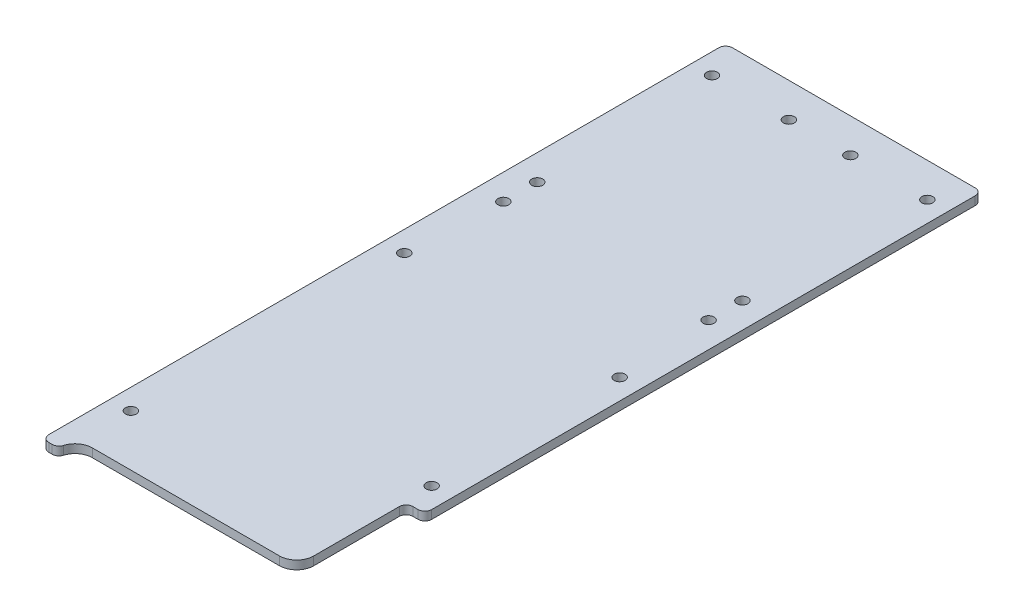
SolidWorks part; units mm, degrees
ref_plane "Front Plane" through (0, 0, 0) normal (0, 0, 1) x (1, 0, 0)
ref_plane "Top Plane" through (0, 0, 0) normal (0, 1, 0) x (1, 0, 0)
ref_plane "Right Plane" through (0, 0, 0) normal (1, 0, 0) x (0, 0, -1)
sketch "Sketch1" plane through (0, 0, 0) normal (0, 1, 0) x (1, 0, 0)
  line L0 (-39.9997, 0) -> (-39.9997, 114.3) construction
  line L1 (-47.625, 127) -> (47.625, 127)
  line L2 (-47.625, 127) -> (-47.625, -127)
  line L3 (-47.625, -127) -> (47.625, -127)
  line L4 (47.625, 127) -> (47.625, -127)
  line L5 (-47.625, 127) -> (47.625, -127) construction
  line L6 (-47.625, -127) -> (47.625, 127) construction
  line L7 (0, 0) -> (0, 127) construction
  line L8 (-39.9997, 0) -> (-39.9997, -101.6) construction
  line L9 (-39.9997, 0) -> (0, 0) construction
  line L10 (-41.275, -127) -> (-41.275, -120.65)
  line L11 (-41.275, -120.65) -> (41.275, -120.65)
  line L12 (41.275, -120.65) -> (41.275, -127)
  line L13 (-39.9997, 114.3) -> (-11.4247, 114.3) construction
  line L14 (39.9997, 114.3) -> (11.4247, 114.3) construction
  circle A0 centre (-39.9997, 114.3) radius 2.032
  circle A1 centre (-39.9997, 0) radius 2.032
  circle A2 centre (-39.9997, -101.6) radius 2.032
  circle A3 centre (39.9997, -101.6) radius 2.032
  circle A4 centre (39.9997, 0) radius 2.032
  circle A5 centre (39.9997, 114.3) radius 2.032
  circle A6 centre (-11.4247, 114.3) radius 2.032
  circle A7 centre (11.4247, 114.3) radius 2.032
  circle A8 centre (-39.9997, -69.85) radius 2.032
  circle A9 centre (39.9997, -69.85) radius 2.032
  point P0 (0, 0)
  dimension "D4" = 4.064
  dimension "D10" = 28.575
  dimension "D1" = 95.25
  dimension "D2" = 254
  dimension "D3" = 7.6253
  dimension "D5" = 12.7
  dimension "D6" = 25.4
  dimension "D7" = 6.35
  dimension "D8" = 6.35
  dimension "D9" = 6.35
  dimension "D11" = 69.85
extrude "Boss-Extrude1" add sketch "Sketch1" along normal blind 3.175 contours L4 L1 L2 L3 A4 A0 A1 A2 A3 A5 | A8 | A3 region at (0, 0, -2.6944) region at (39.9997, 0, 101.6) region at (-39.9997, 0, 69.85)
fillet "Fillet1" radius 2.54 4 edges at (-47.625, 1.5875, -127) (47.625, 1.5875, -127) (47.625, 1.5875, 127) (-47.625, 1.5875, 127)
fillet "Fillet2" radius 2.54 2 edges at (41.275, 1.5875, 127) (-41.275, 1.5875, 127)
fillet "Fillet3" radius 6.35 2 edges at (41.275, 1.5875, 120.65) (-41.275, 1.5875, 120.65)
sketch "Sketch2" plane through (0, 0, 0) normal (0, -1, 0) x (1, 0, 0)
  line L0 (41.9105, 131.8831) -> (41.9105, 109.8659) construction
  line L1 (41.9105, 109.8659) -> (41.9105, 106.3879) construction
  line L2 (41.9105, 83.271) -> (41.9105, 82.5325) construction
  line L3 (41.9105, 82.5325) -> (41.9105, 81.2514) construction
  line L4 (41.9105, 83.271) -> (41.9105, 106.3879) construction
  line L5 (41.9105, 131.8831) -> (41.9105, 109.8659)
  line L6 (41.9105, 109.8659) -> (41.9105, 106.3879)
  line L7 (41.9105, 83.271) -> (41.9105, 82.5325)
  line L8 (41.9105, 82.5325) -> (41.9105, 81.2514)
  line L9 (41.9105, 83.271) -> (41.9105, 106.3879)
  line L10 (41.9105, 81.2514) -> (47.625, 81.2514)
  line L11 (47.625, -124.46) -> (47.625, 124.46) construction
  line L12 (41.9105, 131.8831) -> (47.625, 131.8831)
  line L13 (47.625, 131.8831) -> (47.625, 81.2514)
  line L14 (40.6405, 79.9814) -> (48.895, 79.9814)
  line L15 (48.895, 133.1531) -> (48.895, 79.9814)
  line L16 (40.6405, 133.1531) -> (48.895, 133.1531)
  line L17 (40.6405, 133.1531) -> (40.6405, 109.8659)
  line L18 (40.6405, 109.8659) -> (40.6405, 106.3879)
  line L19 (40.6405, 83.271) -> (40.6405, 106.3879)
  line L20 (40.6405, 83.271) -> (40.6405, 82.5325)
  line L21 (40.6405, 82.5325) -> (40.6405, 79.9814)
  arc M7 (43.815, 127) -> (41.3809, 125.1857) centre (43.815, 124.46) ccw
  arc M8 (41.3809, 125.1857) -> (35.2956, 120.65) centre (35.2956, 127) cw
  line M18 (47.625, -124.46) -> (47.625, 124.46)
  dimension "D1" = 1.27
extrude "Cut-Extrude1" cut sketch "Sketch2" against normal through all contours L20 L21 L14 L10 L8 L7 L9 L19 M18 | L19 L9 L6 L5 L17 L18 M7 M8 | L13 L10 L8 L7 L9 L6 L5 L12 region at (41.6756, 0, 99.9794)
fillet "Fillet4" radius 6.35 1 edges at (40.6405, 1.5875, 123.5715)
fillet "Fillet5" radius 2.54 2 edges at (47.625, 1.5875, 79.9814) (40.6405, 1.5875, 79.9814)
sketch "Sketch3" plane through (0, 0, 0) normal (0, -1, 0) x (1, 0, 0)
  line L0 (-36.31, -49.7791) -> (-39.9168, -49.7791) construction
  line L1 (-40.4248, -49.276) -> (-40.4248, -45.7043) construction
  line L2 (-35.802, -45.7043) -> (-35.802, -49.276) construction
  line L3 (-39.9168, -45.2013) -> (-36.31, -45.2013) construction
  line L4 (-36.31, -37.2027) -> (-39.9168, -37.2027) construction
  line L5 (-35.802, -33.1279) -> (-35.802, -36.6996) construction
  line L6 (-40.4248, -36.6996) -> (-40.4248, -33.1279) construction
  line L7 (-39.9168, -32.6249) -> (-36.31, -32.6249) construction
  line L8 (36.2832, -32.6249) -> (39.89, -32.6249) construction
  line L9 (40.398, -33.1279) -> (40.398, -36.6996) construction
  line L10 (39.89, -37.2027) -> (36.2832, -37.2027) construction
  line L11 (35.7752, -36.6996) -> (35.7752, -33.1279) construction
  line L12 (36.2832, -45.2013) -> (39.89, -45.2013) construction
  line L13 (35.7752, -49.276) -> (35.7752, -45.7043) construction
  line L14 (40.398, -45.7043) -> (40.398, -49.276) construction
  line L15 (39.89, -49.7791) -> (36.2832, -49.7791) construction
  line L16 (-36.31, -49.7791) -> (-39.9168, -49.7791)
  line L17 (-40.4248, -49.276) -> (-40.4248, -45.7043)
  line L18 (-35.802, -45.7043) -> (-35.802, -49.276)
  line L19 (-39.9168, -45.2013) -> (-36.31, -45.2013)
  line L20 (-36.31, -37.2027) -> (-39.9168, -37.2027)
  line L21 (-35.802, -33.1279) -> (-35.802, -36.6996)
  line L22 (-40.4248, -36.6996) -> (-40.4248, -33.1279)
  line L23 (-39.9168, -32.6249) -> (-36.31, -32.6249)
  line L24 (36.2832, -32.6249) -> (39.89, -32.6249)
  line L25 (40.398, -33.1279) -> (40.398, -36.6996)
  line L26 (39.89, -37.2027) -> (36.2832, -37.2027)
  line L27 (35.7752, -36.6996) -> (35.7752, -33.1279)
  line L28 (36.2832, -45.2013) -> (39.89, -45.2013)
  line L29 (35.7752, -49.276) -> (35.7752, -45.7043)
  line L30 (40.398, -45.7043) -> (40.398, -49.276)
  line L31 (39.89, -49.7791) -> (36.2832, -49.7791)
  line L32 (-47.625, -25.836) -> (47.625, -25.836)
  line L33 (-47.625, -124.46) -> (-47.625, 124.46) construction
  line L34 (47.625, -124.46) -> (47.625, 77.4414) construction
  line L35 (0, -25.836) -> (0, -56.0686) construction
  line L38 (134.3608, -51.414) -> (184.1366, -51.414)
  line L39 (184.1366, -51.414) -> (184.1366, -43.4909)
  line L40 (184.1366, -43.4909) -> (182.3332, -43.4909)
  line L41 (181.8252, -42.9878) -> (181.8252, -39.4161)
  line L42 (182.3332, -38.9131) -> (184.1366, -38.9131)
  line L43 (184.1366, -38.9131) -> (184.1366, -30.9899)
  line L44 (184.1366, -30.9899) -> (134.3608, -30.9899)
  line L45 (134.3608, -30.9899) -> (133.3366, -32.0042)
  line L46 (133.3366, -32.0042) -> (132.3124, -30.9899)
  line L47 (132.3124, -30.9899) -> (70.8608, -30.9899)
  line L48 (70.8608, -30.9899) -> (69.8366, -32.0042)
  line L49 (69.8366, -32.0042) -> (68.8124, -30.9899)
  line L50 (68.8124, -30.9899) -> (7.3608, -30.9899)
  line L51 (7.3608, -30.9899) -> (6.3366, -32.0042)
  line L52 (6.3366, -32.0042) -> (5.3124, -30.9899)
  line L53 (5.3124, -30.9899) -> (-56.1392, -30.9899)
  line L54 (-56.1392, -30.9899) -> (-57.1634, -32.0042)
  line L55 (-57.1634, -32.0042) -> (-58.1876, -30.9899)
  line L56 (-58.1876, -30.9899) -> (-119.6392, -30.9899)
  line L57 (-119.6392, -30.9899) -> (-120.6634, -32.0042)
  line L58 (-120.6634, -32.0042) -> (-121.6876, -30.9899)
  line L59 (-121.6876, -30.9899) -> (-184.1634, -30.9899)
  line L60 (-184.1634, -30.9899) -> (-184.1634, -51.414)
  line L61 (-184.1634, -51.414) -> (-121.6876, -51.414)
  line L62 (-121.6876, -51.414) -> (-120.6634, -50.3998)
  line L63 (-120.6634, -50.3998) -> (-119.6392, -51.414)
  line L64 (-119.6392, -51.414) -> (-58.1876, -51.414)
  line L65 (-58.1876, -51.414) -> (-57.1634, -50.3998)
  line L66 (-57.1634, -50.3998) -> (-56.1392, -51.414)
  line L67 (-56.1392, -51.414) -> (5.3124, -51.414)
  line L68 (5.3124, -51.414) -> (6.3366, -50.3998)
  line L69 (6.3366, -50.3998) -> (7.3608, -51.414)
  line L70 (7.3608, -51.414) -> (68.8124, -51.414)
  line L71 (68.8124, -51.414) -> (69.8366, -50.3998)
  line L72 (69.8366, -50.3998) -> (70.8608, -51.414)
  line L73 (70.8608, -51.414) -> (132.3124, -51.414)
  line L74 (132.3124, -51.414) -> (133.3366, -50.3998)
  line L75 (133.3366, -50.3998) -> (134.3608, -51.414)
  line L76 (134.3608, -51.414) -> (184.1366, -51.414)
  line L77 (184.1366, -51.414) -> (184.1366, -43.4909)
  line L78 (184.1366, -43.4909) -> (182.3332, -43.4909)
  line L79 (181.8252, -42.9878) -> (181.8252, -39.4161)
  line L80 (182.3332, -38.9131) -> (184.1366, -38.9131)
  line L81 (184.1366, -38.9131) -> (184.1366, -30.9899)
  line L82 (184.1366, -30.9899) -> (134.3608, -30.9899)
  line L83 (134.3608, -30.9899) -> (133.3366, -32.0042)
  line L84 (133.3366, -32.0042) -> (132.3124, -30.9899)
  line L85 (132.3124, -30.9899) -> (70.8608, -30.9899)
  line L86 (70.8608, -30.9899) -> (69.8366, -32.0042)
  line L87 (69.8366, -32.0042) -> (68.8124, -30.9899)
  line L88 (68.8124, -30.9899) -> (7.3608, -30.9899)
  line L89 (7.3608, -30.9899) -> (6.3366, -32.0042)
  line L90 (6.3366, -32.0042) -> (5.3124, -30.9899)
  line L91 (5.3124, -30.9899) -> (-56.1392, -30.9899)
  line L92 (-56.1392, -30.9899) -> (-57.1634, -32.0042)
  line L93 (-57.1634, -32.0042) -> (-58.1876, -30.9899)
  line L94 (-58.1876, -30.9899) -> (-119.6392, -30.9899)
  line L95 (-119.6392, -30.9899) -> (-120.6634, -32.0042)
  line L96 (-120.6634, -32.0042) -> (-121.6876, -30.9899)
  line L97 (-121.6876, -30.9899) -> (-184.1634, -30.9899)
  line L98 (-184.1634, -30.9899) -> (-184.1634, -51.414)
  line L99 (-184.1634, -51.414) -> (-121.6876, -51.414)
  line L100 (-121.6876, -51.414) -> (-120.6634, -50.3998)
  line L101 (-120.6634, -50.3998) -> (-119.6392, -51.414)
  line L102 (-119.6392, -51.414) -> (-58.1876, -51.414)
  line L103 (-58.1876, -51.414) -> (-57.1634, -50.3998)
  line L104 (-57.1634, -50.3998) -> (-56.1392, -51.414)
  line L105 (-56.1392, -51.414) -> (5.3124, -51.414)
  line L106 (5.3124, -51.414) -> (6.3366, -50.3998)
  line L107 (6.3366, -50.3998) -> (7.3608, -51.414)
  line L108 (7.3608, -51.414) -> (68.8124, -51.414)
  line L109 (68.8124, -51.414) -> (69.8366, -50.3998)
  line L110 (69.8366, -50.3998) -> (70.8608, -51.414)
  line L111 (70.8608, -51.414) -> (132.3124, -51.414)
  line L112 (132.3124, -51.414) -> (133.3366, -50.3998)
  line L113 (133.3366, -50.3998) -> (134.3608, -51.414)
  line L1362 (-40.4248, -34.9138) -> (-35.802, -34.9138)
  line L1857 (-38.1134, -32.6249) -> (-38.1134, -37.2027)
  line L1858 (-38.1134, -45.2013) -> (-38.1134, -49.7791)
  line L1859 (-40.4248, -47.4902) -> (-35.802, -47.4902)
  circle A0 centre (-38.1134, -34.9138) radius 2.032
  circle A1 centre (-38.1134, -47.4902) radius 2.032
  circle A2 centre (38.1134, -47.4902) radius 2.032
  circle A3 centre (38.1134, -34.9138) radius 2.032
  ellipse E0 centre (-39.9168, -45.7043) end of major axis (-39.4088, -45.7043) minor radius 0.5031 (-39.9168, -45.2013) -> (-40.4248, -45.7043) ccw construction
  ellipse E1 centre (-39.9168, -49.276) end of major axis (-39.4088, -49.276) minor radius 0.5031 (-40.4248, -49.276) -> (-39.9168, -49.7791) ccw construction
  ellipse E2 centre (182.3332, -42.9878) end of major axis (182.8412, -42.9878) minor radius 0.5031 (181.8252, -42.9878) -> (182.3332, -43.4909) ccw
  ellipse E3 centre (182.3332, -39.4161) end of major axis (182.8412, -39.4161) minor radius 0.5031 (182.3332, -38.9131) -> (181.8252, -39.4161) ccw
  ellipse E4 centre (182.3332, -42.9878) end of major axis (182.8412, -42.9878) minor radius 0.5031 (181.8252, -42.9878) -> (182.3332, -43.4909) ccw
  ellipse E5 centre (182.3332, -39.4161) end of major axis (182.8412, -39.4161) minor radius 0.5031 (182.3332, -38.9131) -> (181.8252, -39.4161) ccw
  ellipse E6 centre (-36.31, -49.276) end of major axis (-35.802, -49.276) minor radius 0.5031 (-36.31, -49.7791) -> (-35.802, -49.276) ccw construction
  ellipse E7 centre (-36.31, -45.7043) end of major axis (-35.802, -45.7043) minor radius 0.5031 (-35.802, -45.7043) -> (-36.31, -45.2013) ccw construction
  ellipse E8 centre (-39.9168, -36.6996) end of major axis (-39.4088, -36.6996) minor radius 0.5031 (-40.4248, -36.6996) -> (-39.9168, -37.2027) ccw construction
  ellipse E9 centre (-36.31, -36.6996) end of major axis (-35.802, -36.6996) minor radius 0.5031 (-36.31, -37.2027) -> (-35.802, -36.6996) ccw construction
  ellipse E10 centre (-36.31, -33.1279) end of major axis (-35.802, -33.1279) minor radius 0.5031 (-35.802, -33.1279) -> (-36.31, -32.6249) ccw construction
  ellipse E11 centre (-39.9168, -33.1279) end of major axis (-39.4088, -33.1279) minor radius 0.5031 (-39.9168, -32.6249) -> (-40.4248, -33.1279) ccw construction
  ellipse E12 centre (39.89, -33.1279) end of major axis (40.398, -33.1279) minor radius 0.5031 (40.398, -33.1279) -> (39.89, -32.6249) ccw construction
  ellipse E13 centre (36.2832, -33.1279) end of major axis (36.7912, -33.1279) minor radius 0.5031 (36.2832, -32.6249) -> (35.7752, -33.1279) ccw construction
  ellipse E14 centre (39.89, -36.6996) end of major axis (40.398, -36.6996) minor radius 0.5031 (39.89, -37.2027) -> (40.398, -36.6996) ccw construction
  ellipse E15 centre (36.2832, -36.6996) end of major axis (36.7912, -36.6996) minor radius 0.5031 (35.7752, -36.6996) -> (36.2832, -37.2027) ccw construction
  ellipse E16 centre (36.2832, -45.7043) end of major axis (36.7912, -45.7043) minor radius 0.5031 (36.2832, -45.2013) -> (35.7752, -45.7043) ccw construction
  ellipse E17 centre (36.2832, -49.276) end of major axis (36.7912, -49.276) minor radius 0.5031 (35.7752, -49.276) -> (36.2832, -49.7791) ccw construction
  ellipse E18 centre (39.89, -45.7043) end of major axis (40.398, -45.7043) minor radius 0.5031 (40.398, -45.7043) -> (39.89, -45.2013) ccw construction
  ellipse E19 centre (39.89, -49.276) end of major axis (40.398, -49.276) minor radius 0.5031 (39.89, -49.7791) -> (40.398, -49.276) ccw construction
  ellipse E20 centre (-39.9168, -45.7043) end of major axis (-39.4088, -45.7043) minor radius 0.5031 (-39.9168, -45.2013) -> (-40.4248, -45.7043) ccw
  ellipse E21 centre (-39.9168, -49.276) end of major axis (-39.4088, -49.276) minor radius 0.5031 (-40.4248, -49.276) -> (-39.9168, -49.7791) ccw
  ellipse E22 centre (-36.31, -49.276) end of major axis (-35.802, -49.276) minor radius 0.5031 (-36.31, -49.7791) -> (-35.802, -49.276) ccw
  ellipse E23 centre (-36.31, -45.7043) end of major axis (-35.802, -45.7043) minor radius 0.5031 (-35.802, -45.7043) -> (-36.31, -45.2013) ccw
  ellipse E24 centre (-39.9168, -36.6996) end of major axis (-39.4088, -36.6996) minor radius 0.5031 (-40.4248, -36.6996) -> (-39.9168, -37.2027) ccw
  ellipse E25 centre (-36.31, -36.6996) end of major axis (-35.802, -36.6996) minor radius 0.5031 (-36.31, -37.2027) -> (-35.802, -36.6996) ccw
  ellipse E26 centre (-36.31, -33.1279) end of major axis (-35.802, -33.1279) minor radius 0.5031 (-35.802, -33.1279) -> (-36.31, -32.6249) ccw
  ellipse E27 centre (-39.9168, -33.1279) end of major axis (-39.4088, -33.1279) minor radius 0.5031 (-39.9168, -32.6249) -> (-40.4248, -33.1279) ccw
  ellipse E28 centre (39.89, -33.1279) end of major axis (40.398, -33.1279) minor radius 0.5031 (40.398, -33.1279) -> (39.89, -32.6249) ccw
  ellipse E29 centre (36.2832, -33.1279) end of major axis (36.7912, -33.1279) minor radius 0.5031 (36.2832, -32.6249) -> (35.7752, -33.1279) ccw
  ellipse E30 centre (39.89, -36.6996) end of major axis (40.398, -36.6996) minor radius 0.5031 (39.89, -37.2027) -> (40.398, -36.6996) ccw
  ellipse E31 centre (36.2832, -36.6996) end of major axis (36.7912, -36.6996) minor radius 0.5031 (35.7752, -36.6996) -> (36.2832, -37.2027) ccw
  ellipse E32 centre (36.2832, -45.7043) end of major axis (36.7912, -45.7043) minor radius 0.5031 (36.2832, -45.2013) -> (35.7752, -45.7043) ccw
  ellipse E33 centre (36.2832, -49.276) end of major axis (36.7912, -49.276) minor radius 0.5031 (35.7752, -49.276) -> (36.2832, -49.7791) ccw
  ellipse E34 centre (39.89, -45.7043) end of major axis (40.398, -45.7043) minor radius 0.5031 (40.398, -45.7043) -> (39.89, -45.2013) ccw
  ellipse E35 centre (39.89, -49.276) end of major axis (40.398, -49.276) minor radius 0.5031 (39.89, -49.7791) -> (40.398, -49.276) ccw
  dimension "D2" = 4.064
  dimension "D1" = 0
extrude "Cut-Extrude2" cut sketch "Sketch3" against normal through all contours A0 | A1 | A2 | A3
